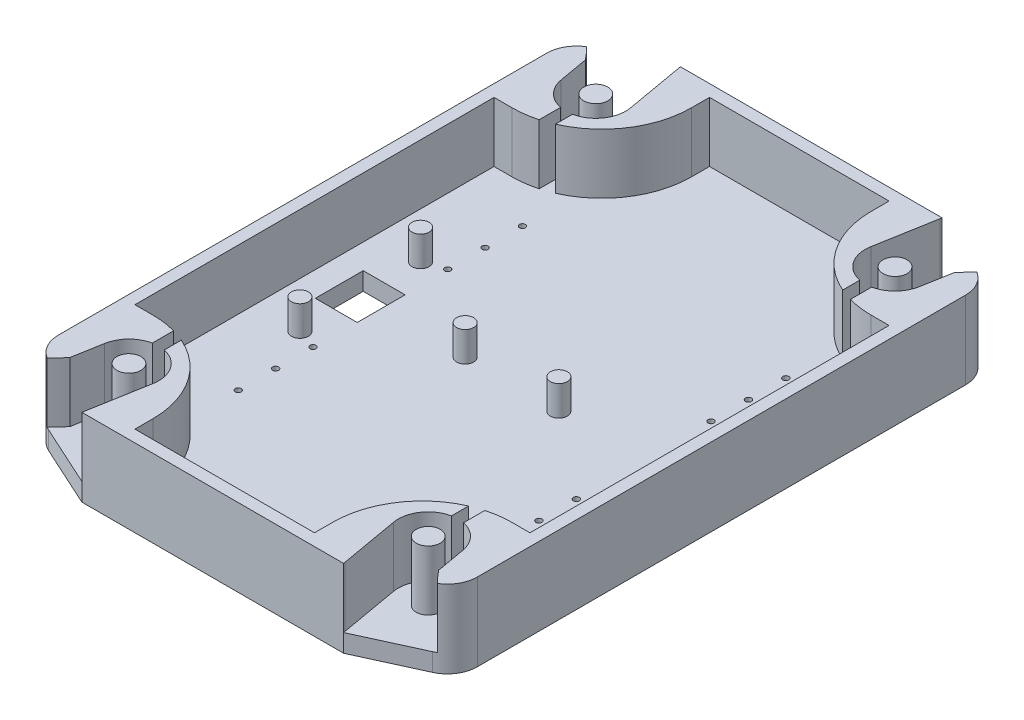
SolidWorks part; units mm, degrees
ref_plane "Alzado" through (0, 0, 0) normal (0, 0, 1) x (1, 0, 0)
ref_plane "Planta" through (0, 0, 0) normal (0, 1, 0) x (1, 0, 0)
ref_plane "Vista lateral" through (0, 0, 0) normal (1, 0, 0) x (0, 0, -1)
sketch "Croquis2" plane through (0, 0, 0) normal (0, 0, 1) x (1, 0, 0)
  line L0 (0, -6.2203) -> (0, 18.321) construction
  line L1 (-35, 1.5) -> (35, 1.5)
  line L2 (-35, 1.5) -> (-35, -1.5)
  line L3 (-35, -1.5) -> (35, -1.5)
  line L4 (35, 1.5) -> (35, -1.5)
  line L5 (-35, 1.5) -> (35, -1.5) construction
  line L6 (-35, -1.5) -> (35, 1.5) construction
  point P0 (0, 0)
  dimension "D1" = 70
  dimension "D2" = 3
extrude "Saliente-Extruir1" add sketch "Croquis2" along normal blind 100
sketch "Croquis3" plane through (0, 1.5, 0) normal (0, 1, 0) x (1, 0, 0)
  line L1 (-35, 0) -> (-15, 0)
  line L2 (-35, 0) -> (-35, -20)
  line L3 (-35, -20) -> (-15, -20)
  line L4 (-15, 0) -> (-15, -20)
  line L5 (35, 0) -> (15, 0)
  line L6 (35, 0) -> (35, -20)
  line L7 (35, -20) -> (15, -20)
  line L8 (15, 0) -> (15, -20)
  line L9 (35, -100) -> (15, -100)
  line L10 (35, -100) -> (35, -80)
  line L11 (35, -80) -> (15, -80)
  line L12 (15, -100) -> (15, -80)
  line L13 (-35, -100) -> (-15, -100)
  line L14 (-35, -100) -> (-35, -80)
  line L15 (-35, -80) -> (-15, -80)
  line L16 (-15, -100) -> (-15, -80)
  dimension "D1" = 20
  dimension "D2" = 20
  dimension "D3" = 20
  dimension "D4" = 20
  dimension "D5" = 20
  dimension "D6" = 20
  dimension "D7" = 20
  dimension "D8" = 20
extrude "Saliente-Extruir2" add sketch "Croquis3" along normal blind 10
sketch "Croquis4" plane through (0, 1.5, 0) normal (0, 1, 0) x (1, 0, 0)
  line L0 (0, -100) -> (0, -79.5641) construction
  line L1 (15, -100) -> (-15, -100) construction
  line L2 (15, -80) -> (15, -100) construction
  line L3 (-15, -88) -> (15, -88)
  line L4 (-15, -88) -> (-15, -98)
  line L5 (-15, -98) -> (15, -98)
  line L6 (15, -88) -> (15, -98)
  line L7 (-15, -88) -> (15, -98) construction
  line L8 (-15, -98) -> (15, -88) construction
  point P5 (0, -93)
  dimension "D1" = 2
  dimension "D2" = 10
extrude "Cortar-Extruir1" cut sketch "Croquis4" against normal blind 10
sketch "Croquis6" plane through (0, -1.5, 0) normal (0, -1, 0) x (1, 0, 0)
  line L0 (-15, 88) -> (-15, 16) construction
  line L1 (-15, 16) -> (15, 16) construction
  line L2 (15, 16) -> (15, 88) construction
  line L3 (15, 88) -> (-15, 88) construction
  line L4 (0, -7.15) -> (0, 7.15) construction
  line L5 (-15, 80) -> (-25, 80)
  line L6 (-15, 80) -> (-15, 55)
  line L7 (-15, 55) -> (-25, 55)
  line L8 (-25, 80) -> (-25, 55)
  line L9 (-15, 20) -> (-25, 20)
  line L10 (-15, 20) -> (-15, 45)
  line L11 (-15, 45) -> (-25, 45)
  line L12 (-25, 20) -> (-25, 45)
  line L13 (15, 45) -> (25, 45)
  line L14 (25, 20) -> (25, 45)
  line L15 (15, 20) -> (25, 20)
  line L16 (15, 20) -> (15, 45)
  line L17 (15, 55) -> (25, 55)
  line L18 (25, 80) -> (25, 55)
  line L19 (15, 80) -> (25, 80)
  line L20 (15, 80) -> (15, 55)
  dimension "D1" = 72
  dimension "D2" = 10
  dimension "D3" = 25
  dimension "D4" = 10
  dimension "D5" = 25
  dimension "D6" = 8
  dimension "D7" = 4
extrude "Cortar-Extruir6" cut sketch "Croquis6" against normal blind 1.5
sketch "Croquis7" plane through (0, 1.5, 0) normal (0, 1, 0) x (1, 0, 0)
  line L0 (-25.3586, -38.5) -> (-25.3586, -61.5) construction
  line L6 (-27.6124, -61.5) -> (-22.2229, -61.5) construction
  line L7 (-28.8402, -38.5) -> (-18.5871, -38.5) construction
  line L10 (-35, -20) -> (-15, -20) construction
  circle A2 centre (-25.3586, -60.075) radius 1.425
  circle A3 centre (-25.3586, -39.925) radius 1.425
  point P18 (-25.3586, -50)
  dimension "D2" = 2.85
  dimension "D1" = 2.85
  dimension "D3" = 23
  dimension "D4" = 30
extrude "Saliente-Extruir3" add sketch "Croquis7" along normal blind 5
sketch "Croquis9" plane through (0, 1.5, 0) normal (0, 1, 0) x (1, 0, 0)
  line L0 (0, 0) -> (0, -50) construction
  line L1 (-9.25, -50) -> (9.25, -50) construction
  line L2 (-9.25, -50) -> (-9.25, -46.9521) construction
  line L3 (9.25, -50) -> (9.25, -14.173) construction
  circle A2 centre (-7.825, -50) radius 1.425
  circle A3 centre (7.825, -50) radius 1.425
  point P2 (0, -50)
  dimension "D1" = 50
  dimension "D4" = 2.85
  dimension "D5" = 2.85
  dimension "D3" = 18.5
extrude "Saliente-Extruir4" add sketch "Croquis9" along normal blind 5
sketch "Croquis11" plane through (0, 1.5, 0) normal (0, 1, 0) x (1, 0, 0)
  line L0 (-25.3586, -39.925) -> (-25.3586, -60.075) construction
  line L2 (-28.8586, -46) -> (-21.8586, -46)
  line L3 (-28.8586, -46) -> (-28.8586, -54)
  line L4 (-28.8586, -54) -> (-21.8586, -54)
  line L5 (-21.8586, -46) -> (-21.8586, -54)
  line L6 (-28.8586, -46) -> (-21.8586, -54) construction
  line L7 (-28.8586, -54) -> (-21.8586, -46) construction
  point P4 (-25.3586, -50)
  dimension "D1" = 7
  dimension "D2" = 8
extrude "Cortar-Extruir8" cut sketch "Croquis11" against normal blind 5
sketch "Croquis12" plane through (0, 1.5, 0) normal (0, 1, 0) x (1, 0, 0)
  line L0 (-35, -20) -> (-35, -80)
  line L1 (-35, -80) -> (-33, -80)
  line L2 (-15, -80) -> (-35, -80) construction
  line L3 (-33, -80) -> (-33, -20)
  line L4 (-35, -20) -> (-15, -20) construction
  line L5 (-33, -20) -> (-35, -20)
  line L6 (-15, -98) -> (-15, -100)
  line L7 (-15, -100) -> (15, -100)
  line L8 (15, -100) -> (15, -98)
  line L9 (15, -98) -> (-15, -98)
  line L10 (35, -80) -> (35, -20)
  line L11 (35, -20) -> (33, -20)
  line L12 (15, -20) -> (35, -20) construction
  line L13 (33, -20) -> (33, -80)
  line L14 (35, -80) -> (15, -80) construction
  line L15 (33, -80) -> (35, -80)
  line L16 (-15, 0) -> (15, 0)
  line L17 (15, 0) -> (15, -2)
  line L18 (15, 0) -> (15, -20) construction
  line L19 (15, -2) -> (-15, -2)
  line L20 (-15, -20) -> (-15, 0) construction
  line L21 (-15, -2) -> (-15, 0)
  dimension "D1" = 2
  dimension "D2" = 2
  dimension "D3" = 2
extrude "Saliente-Extruir5" add sketch "Croquis12" along normal up to vertex (10 mm away) up to point (-35, 11.5, 20)
sketch "Croquis13" plane through (0, 11.5, 0) normal (0, 1, 0) x (1, 0, 0)
  line L0 (-15, -11) -> (-35, -11) construction
  line L1 (-15, -20) -> (-15, -2) construction
  line L2 (-35, 0) -> (-35, -100) construction
  line L3 (-25, -20) -> (-25, 0) construction
  line L4 (-33, -20) -> (-15, -20) construction
  line L5 (35, 0) -> (-35, 0) construction
  line L6 (-25, -11) -> (-26.7365, -1.1519) construction
  line L7 (-29.924, -11.8682) -> (-31.6605, -2.0202)
  line L8 (-20.076, -10.1318) -> (-21.8124, -0.2837)
  line L9 (0, -7.15) -> (0, 7.15) construction
  line L10 (25, -11) -> (26.7365, -1.1519) construction
  line L11 (29.924, -11.8682) -> (31.6605, -2.0202)
  line L12 (20.076, -10.1318) -> (21.8124, -0.2837)
  arc A0 (-29.924, -11.8682) -> (-20.076, -10.1318) centre (-25, -11) ccw
  arc A1 (-21.8124, -0.2837) -> (-31.6605, -2.0202) centre (-26.7365, -1.1519) ccw
  circle A2 centre (-25, -11) radius 2
  circle A3 centre (25, -11) radius 2
  arc A4 (29.924, -11.8682) -> (20.076, -10.1318) centre (25, -11) cw
  arc A5 (21.8124, -0.2837) -> (31.6605, -2.0202) centre (26.7365, -1.1519) cw
  point P14 (-25.8682, -6.076)
  point P26 (25.8682, -6.076)
  dimension "D3" = 5
  dimension "D4" = 4
  dimension "D1" = 10
  dimension "D2" = 10
ref_plane "Plano2" through (0, 0, 50) normal (0, 0, -1) x (-1, 0, 0)
extrude "Cortar-Extruir9" cut sketch "Croquis13" against normal blind 10
mirror "Simetría1" about plane through (0, 0, 50) normal (0, 0, -1) of "Cortar-Extruir9"
sketch "Croquis14" plane through (0, 11.5, 0) normal (0, 1, 0) x (1, 0, 0)
  line L0 (-31.6605, -2.0202) -> (-29.924, -11.8682) construction
  line L1 (-30.7923, -6.9442) -> (-30.7923, 3.6329)
  line L2 (-30.7923, 3.6329) -> (-47.5168, 3.6329)
  line L3 (-47.5168, 3.6329) -> (-47.5168, 0)
  line L5 (0, -7.15) -> (0, 7.15) construction
  line L6 (30.7923, 3.6329) -> (47.5168, 3.6329)
  line L7 (30.7923, -6.9442) -> (30.7923, 3.6329)
  line L8 (47.5168, 3.6329) -> (47.5168, 0)
  spline S0 degree 2 poles (-30.7923, -6.9442) (-37.6805, 1.5747) (-47.5168, 0) knots 0 0 0 1 1 1
  spline S1 degree 2 poles (30.7923, -6.9442) (37.6805, 1.5747) (47.5168, 0) knots 0 0 0 1 1 1
extrude "Cortar-Extruir10" cut sketch "Croquis14" against normal blind 10
mirror "Simetría2" about plane through (0, 0, 50) normal (0, 0, -1) of "Cortar-Extruir10"
fillet "Redondeo1" radius 15 4 edges at (-15, 6.5, 80) (-15, 6.5, 20) (15, 6.5, 20) (15, 6.5, 80)
sketch "Croquis16" plane through (0, 1.5, 0) normal (0, 1, 0) x (1, 0, 0)
  line L0 (-21.871, -100) -> (-35, -94)
  line L1 (-35, -2.8777) -> (-35, -97.1223) construction
  line L2 (-35, -94) -> (-35, -100)
  line L3 (-35, -100) -> (-21.871, -100)
  line L4 (0, -7.15) -> (0, 7.15) construction
  line L5 (35, -94) -> (35, -100)
  line L6 (21.871, -100) -> (35, -94)
  line L7 (35, -100) -> (21.871, -100)
  dimension "D1" = 6
extrude "Cortar-Extruir11" cut sketch "Croquis16" against normal through all both and the other way through all
mirror "Simetría3" about plane through (0, 0, 50) normal (0, 0, -1) of "Cortar-Extruir11"
fillet "Redondeo4" radius 5 4 edges at (35, 5, 94) (-35, 5, 94) (35, 5, 6) (-35, 5, 6)
sketch "Croquis17" plane through (0, -1.5, 0) normal (0, -1, 0) x (1, 0, 0)
  line L0 (-30.7242, 85.2653) -> (-23.0168, 91.6368) construction
  line L1 (-32.317, 87.1922) -> (-24.6096, 93.5636)
  line L2 (-29.1313, 83.3385) -> (-21.4239, 89.7099)
  arc A0 (-32.317, 87.1922) -> (-29.1313, 83.3385) centre (-30.7242, 85.2653) ccw
  arc A1 (-21.4239, 89.7099) -> (-24.6096, 93.5636) centre (-23.0168, 91.6368) ccw
  point P2 (-26.8705, 88.4511)
  point P7 (-28.4633, 90.3779)
  dimension "D1" = 10
  dimension "D2" = 5
extrude "Cortar-Extruir12" cut sketch "Croquis17" against normal blind 1.5
sketch "Croquis18" plane through (0, 0, 0) normal (0, -1, 0) x (1, 0, 0)
  circle A0 centre (-30.7242, 85.2653) radius 1
  circle A1 centre (-23.0168, 91.6368) radius 1
  dimension "D1" = 2
  dimension "D2" = 2
extrude "Cortar-Extruir13" cut sketch "Croquis18" against normal blind 1
mirror "Simetría4" about plane through (0, 0, 0) normal (1, 0, 0) of "Cortar-Extruir13", "Cortar-Extruir12"
mirror "Simetría5" about plane through (0, 0, 50) normal (0, 0, -1) of "Simetría4"
sketch "Croquis19" plane through (0, 11.5, 0) normal (0, 1, 0) x (1, 0, 0)
  line L0 (-25, -11) -> (-25, -25.2725) construction
  line L1 (0, -7.15) -> (0, 7.15) construction
  line L2 (-24, -22.9106) -> (-26, -22.9106)
  line L3 (-24, -22.9106) -> (-24, -13.362)
  line L4 (-24, -13.362) -> (-26, -13.362)
  line L5 (-26, -22.9106) -> (-26, -13.362)
  line L6 (-24, -22.9106) -> (-26, -13.362) construction
  line L7 (-24, -13.362) -> (-26, -22.9106) construction
  line L8 (24, -13.362) -> (26, -13.362)
  line L9 (26, -22.9106) -> (26, -13.362)
  line L10 (24, -22.9106) -> (26, -22.9106)
  line L11 (24, -22.9106) -> (24, -13.362)
  point P3 (-25, -18.1363)
  dimension "D1" = 2
extrude "Cortar-Extruir14" cut sketch "Croquis19" against normal blind 10
mirror "Simetría6" about plane through (0, 0, 50) normal (0, 0, -1) of "Cortar-Extruir14"
sketch "Croquis24" plane through (0, 0, 0) normal (0, -1, 0) x (1, 0, 0)
  line L0 (-25, 20) -> (-19, 20) construction
  line L1 (-19, 100) -> (-19, 20) construction
  line L2 (-25, 20) -> (-15, 20) construction
  line L3 (-22, 20.9603) -> (-22, 41.3381) construction
  circle A0 centre (-22, 38.75) radius 0.5
  circle A1 centre (-22, 32.5) radius 0.5
  circle A2 centre (-22, 26.25) radius 0.5
extrude "Cortar-Extruir18" cut sketch "Croquis24" against normal blind 10
sketch "Croquis25" plane through (0, 0, 0) normal (0, -1, 0) x (1, 0, 0)
  circle A0 centre (-22, 73.75) radius 0.5
  circle A1 centre (-22, 67.5) radius 0.5
  circle A2 centre (-22, 61.25) radius 0.5
extrude "Cortar-Extruir19" cut sketch "Croquis25" against normal blind 10
sketch "Croquis26" plane through (0, 0, 0) normal (0, -1, 0) x (1, 0, 0)
  circle A0 centre (22, 73.75) radius 0.5
  circle A1 centre (22, 67.5) radius 0.5
  circle A2 centre (22, 61.25) radius 0.5
  circle A3 centre (22, 38.75) radius 0.5
  circle A4 centre (22, 32.5) radius 0.5
  circle A5 centre (22, 26.25) radius 0.5
extrude "Cortar-Extruir20" cut sketch "Croquis26" against normal blind 10
